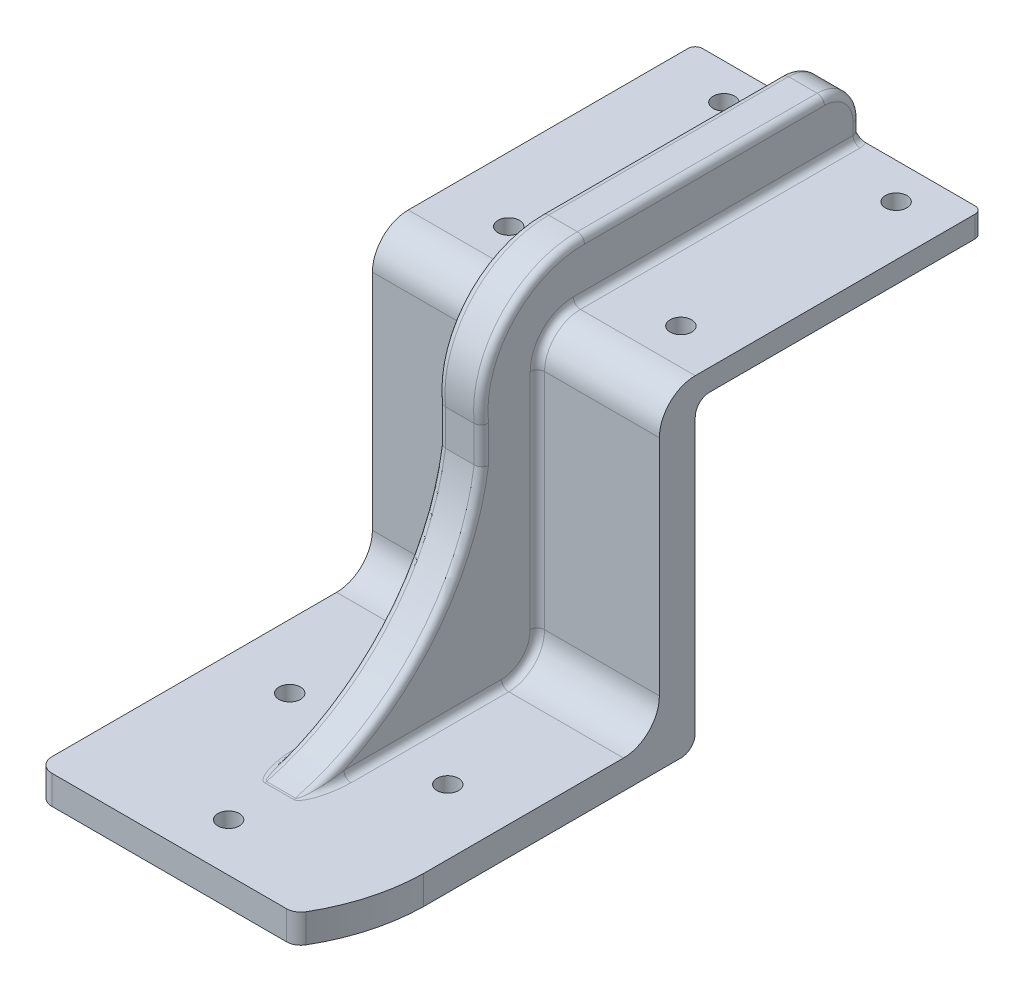
SolidWorks part; units mm, degrees
material "Plastique personnalisé"
ref_plane "Plan de face" through (0, 0, 0) normal (0, 0, 1) x (1, 0, 0)
ref_plane "Plan de dessus" through (0, 0, 0) normal (0, 1, 0) x (1, 0, 0)
ref_plane "Plan de droite" through (0, 0, 0) normal (1, 0, 0) x (0, 0, -1)
sketch "Esquisse1" plane through (0, 0, 0) normal (0, 1, 0) x (1, 0, 0)
  line L1 (0, 0) -> (40, 0)
  line L2 (0, 0) -> (0, 39)
  line L3 (1, 40) -> (39, 40)
  line L4 (40, 0) -> (40, 39)
  arc A0 (39, 40) -> (40, 39) centre (39, 39) cw
  arc A1 (0, 39) -> (1, 40) centre (1, 39) cw
  point P7 (40, 40)
  point P10 (0, 40)
  dimension "D3" = 1
  dimension "D1" = 40
  dimension "D2" = 40
extrude "Boss.-Extru.1" add sketch "Esquisse1" along normal blind 3
sketch "Esquisse2" plane through (0, 3, 0) normal (0, 1, 0) x (1, 0, 0)
  line L0 (0, 0) -> (0, -5)
  line L1 (0, -5) -> (40, -5)
  line L5 (40, -5) -> (40, 0)
  line L6 (0, 0) -> (40, 0) construction
  line L7 (40, 0) -> (0, 0)
  dimension "D1" = 5
  dimension "D2" = 40
extrude "Boss.-Extru.2" add sketch "Esquisse2" against normal up to surface (45.1571 mm away)
sketch "Esquisse3" plane through (0, -42.1571, 0) normal (0, -1, 0) x (1, 0, 0)
  line L1 (0, 0) -> (40, 0)
  line L2 (0, 0) -> (0, 51.6693)
  line L3 (0, 51.6693) -> (40, 51.6693)
  line L4 (40, 0) -> (40, 51.6693)
  dimension "D1" = 40
extrude "Boss.-Extru.3" add sketch "Esquisse3" against normal blind 4
fillet "Congé3" radius 5 2 edges at (20, -38.1571, 5) (20, 3, 5)
fillet "Congé5" radius 2 2 edges at (40, -40.1571, 51.6693) (0, -40.1571, 51.6693)
fillet "Congé6" radius 2 2 edges at (20, -42.1571, 0) (20, 0, 0)
sketch "Esquisse4" plane through (0, -38.1571, 0) normal (0, 1, 0) x (1, 0, 0)
  line L0 (40, -10) -> (40, -49.6693) construction
  line L1 (38, -51.6693) -> (2, -51.6693) construction
  line L2 (35.8196, -51.6693) -> (38, -51.6693)
  line L3 (40, -49.6693) -> (40, -37.8612)
  arc A0 (40, -37.8612) -> (35.8196, -51.6693) centre (13.9, -37.4963) cw
  arc A1 (38, -51.6693) -> (40, -49.6693) centre (38, -49.6693) ccw
extrude "Enlèv. mat.-Extru.1" cut sketch "Esquisse4" against normal blind 10
fillet "Congé7" radius 2 1 edges at (35.8196, -40.1571, 51.6693)
sketch "Esquisse6" plane through (0, 3, 0) normal (0, 1, 0) x (1, 0, 0)
  circle A0 centre (8.9991, 34.998) radius 1.5
  circle A1 centre (32.9981, 34.998) radius 1.5
  circle A2 centre (32.9981, 5.002) radius 1.5
  circle A3 centre (8.9991, 5.002) radius 1.5
extrude "Enlèv. mat.-Extru.3" cut sketch "Esquisse6" against normal blind 10
ref_plane "Plan1" through (20, 0, 0) normal (1, 0, 0) x (0, 0, -1)
sketch "Esquisse7" plane through (20, 0, 0) normal (1, 0, 0) x (0, 0, -1)
  line L0 (-37.8612, -38.1571) -> (-5, -38.1571)
  line L1 (-5, -2) -> (-5, -38.1571)
  line L2 (1.5686, 8.0941) -> (1.5686, 10.5941) construction
  line L3 (-12.8124, -5.3622) -> (-12.8124, -10.3622)
  line L4 (-5.9734, -5.3622) -> (-12.8124, -5.3622) construction
  line L5 (1.5686, 10.5941) -> (40, 10.5941)
  line L6 (40, 10.5941) -> (40, 3)
  line L7 (40, 3) -> (0, 3)
  arc A0 (1.5686, 10.5941) -> (-12.8124, -5.3622) centre (1.5048, -3.8072) ccw
  arc A1 (-12.8124, -10.3622) -> (-37.8612, -38.1571) centre (-46.1838, -5.4723) cw
  arc A2 (-5, -2) -> (0, 3) centre (0, -2) cw
  dimension "D1" = 2.5
  dimension "D2" = 5
extrude "Boss.-Extru.4" add sketch "Esquisse7" along normal blind 3 and the other way blind 3
fillet "Congé10" radius 5 1 edges at (20, 10.5941, -40)
fillet "Congé11" radius 1 12 edges at (17, 4.297, -40) (17, 9.1296, -38.5355) (23, 4.297, -40) (17, 10.5941, -18.2843) (17, 5.8344, 9.1929) (17, -7.8622, 12.8124) (17, -28.0516, 21.1292) (23, -28.0516, 21.1292) (23, -7.8622, 12.8124) (23, 5.8344, 9.1929) (23, 10.5941, -18.2843) (23, 9.1296, -38.5355)
fillet "Congé12" radius 1 15 edges at (17.2929, 3, -39.7071) (17, 3, -19.5) (17, 1.5355, 3.5355) (17, -17.5785, 5) (17, -36.6926, 6.4645) (17, -38.1571, 22.2242) (17.7912, -38.1571, 37.7723) (20, -38.1571, 37.8612) (22.3377, -38.1571, 37.6263) (23, -38.1571, 22.2242) (22.7071, 3, -39.7071) (23, 3, -19.5) (23, 1.5355, 3.5355) (23, -17.5785, 5) (23, -36.6926, 6.4645)
sketch "Esquisse8" plane through (0, -38.1571, 0) normal (0, 1, 0) x (1, 0, 0)
  circle A0 centre (8.9117, -25.4329) radius 1.5003
  circle A1 centre (30.9385, -25.4329) radius 1.4967
  circle A2 centre (19.9251, -44.9651) radius 1.5018
extrude "Enlèv. mat.-Extru.4" cut sketch "Esquisse8" against normal blind 10
